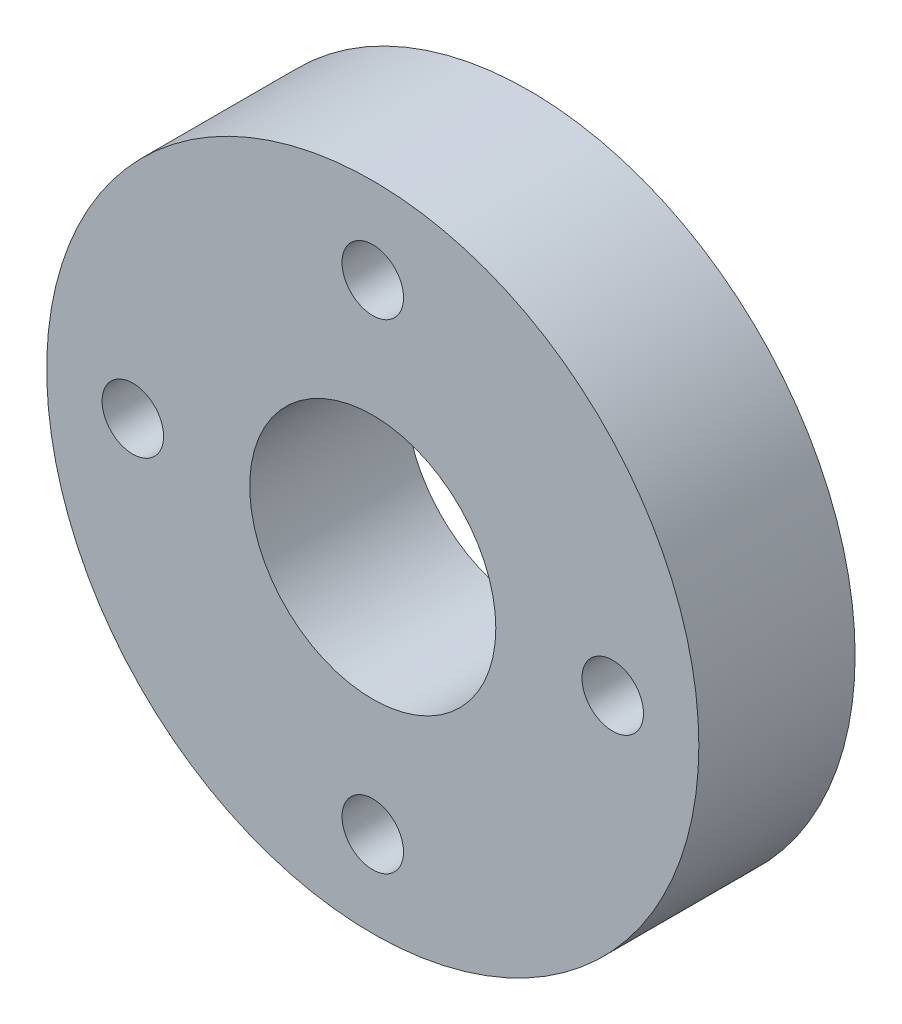
SolidWorks part; units mm, degrees
ref_plane "Front Plane" through (0, 0, 0) normal (0, 0, 1) x (1, 0, 0)
ref_plane "Top Plane" through (0, 0, 0) normal (0, 1, 0) x (1, 0, 0)
ref_plane "Right Plane" through (0, 0, 0) normal (1, 0, 0) x (0, 0, -1)
sketch "Sketch3" plane through (0, 0, 0) normal (0, 0, 1) x (1, 0, 0)
  circle A0 centre (0, 0) radius 13.25
  dimension "D1" = 26.5
extrude "Boss-Extrude1" add sketch "Sketch3" along normal blind 6.35
sketch "Sketch4" plane through (0, 0, 6.35) normal (0, 0, 1) x (1, 0, 0)
  circle A0 centre (0, 0) radius 5
  circle A1 centre (0, 0) radius 9.75 construction
  circle A2 centre (0, 9.75) radius 1.25
  circle A3 centre (9.75, 0) radius 1.25
  circle A4 centre (0, -9.75) radius 1.25
  circle A5 centre (-9.75, 0) radius 1.25
  point P6 (0, 0)
  point P7 (0, 0)
  point P15 (0, 0)
  dimension "D1" = 10
  dimension "D2" = 19.5
  dimension "D3" = 2.5
  dimension "D4" = 4
extrude "Cut-Extrude1" cut sketch "Sketch4" against normal blind 6.35
